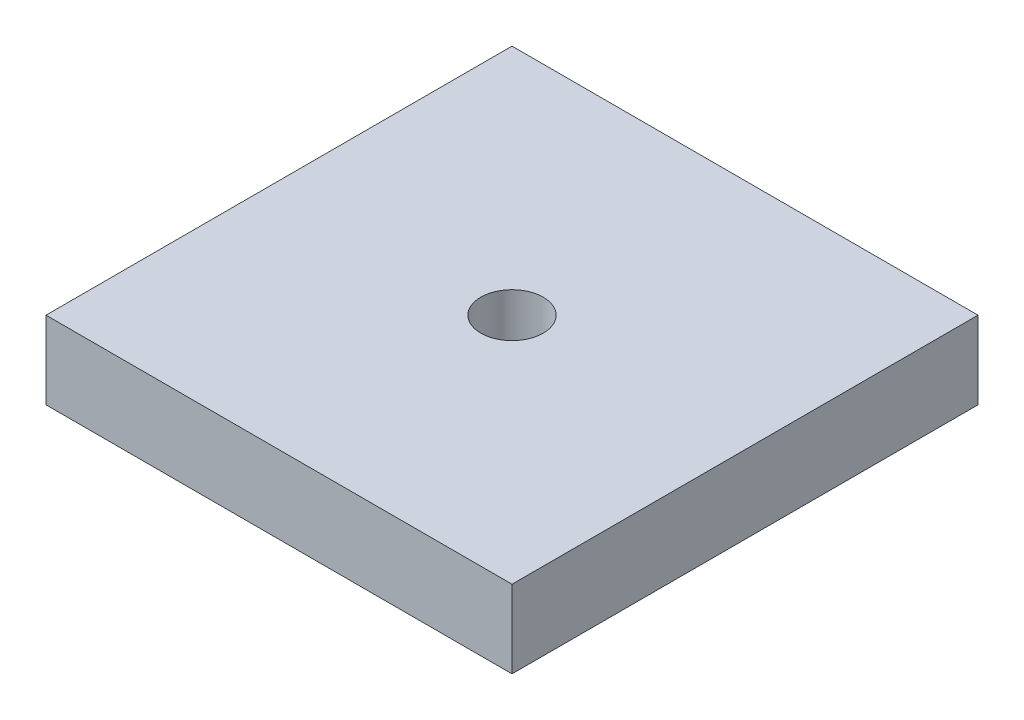
SolidWorks part; units mm, degrees
material "6061-T6 (SS)"
ref_plane "Front" through (0, 0, 0) normal (0, 0, 1) x (1, 0, 0)
ref_plane "Top" through (0, 0, 0) normal (0, 1, 0) x (1, 0, 0)
ref_plane "Right" through (0, 0, 0) normal (1, 0, 0) x (0, 0, -1)
sketch "Sketch1" plane through (0, 0, 0) normal (0, 1, 0) x (1, 0, 0)
  line L1 (0, 0) -> (38.1, 0)
  line L2 (0, 0) -> (0, 38.1)
  line L3 (0, 38.1) -> (38.1, 38.1)
  line L4 (38.1, 0) -> (38.1, 38.1)
  dimension "D1" = 38.1
extrude "Boss-Extrude1" add sketch "Sketch1" along normal blind 6.35
sketch "Sketch4" plane through (0, 6.35, 0) normal (0, 1, 0) x (1, 0, 0)
  line L0 (0, 38.1) -> (38.1, 0) construction
  point P0 (19.05, 19.05)
hole_wizard "1/4-20 Tapped Hole1" positions "Sketch4" profile "Sketch3" tap size "1/4-20" standard "ANSI Inch"
sketch "Sketch3" plane through (19.05, 6.35, -19.05) normal (1, 0, 0) x (0, 0, 1)
  line L0 (0, 0) -> (0, 18.0438)
  line L1 (0, 18.0438) -> (2.5527, 16.51)
  line L2 (2.5527, 16.51) -> (2.5527, 0)
  line L5 (2.5527, 0) -> (0, 0)
  line L10 (0, 18.0438) -> (-2.5527, 16.51) construction
  line L11 (0, -6.35) -> (0, 107.95) construction
  dimension "Tap Drill Dia." = 5.1054
  dimension "Tap Drill Depth" = 16.51
  dimension "Drill Angle" = 118
cosmetic thread "Hole Thread1" parameters "D1"=12.7, "D2"=6.35
